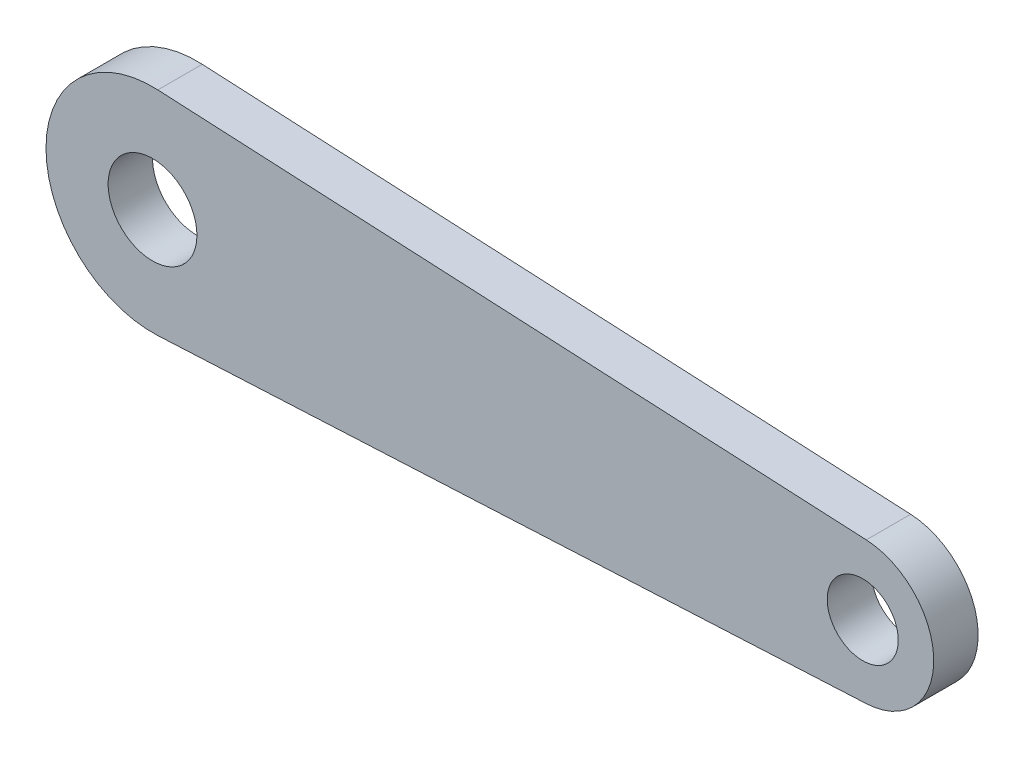
SolidWorks part; units mm, degrees
material "PE High Density"
ref_plane "Front Plane" through (0, 0, 0) normal (0, 0, 1) x (1, 0, 0)
ref_plane "Top Plane" through (0, 0, 0) normal (0, 1, 0) x (1, 0, 0)
ref_plane "Right Plane" through (0, 0, 0) normal (1, 0, 0) x (0, 0, -1)
sketch "Sketch1" plane through (0, 0, 0) normal (0, 0, 1) x (1, 0, 0)
  line L0 (0, -994.956) -> (0, 48752.8433) construction
  line L1 (0.381, 7.6105) -> (51.054, 5.0736)
  line L2 (51.054, -5.0736) -> (0.381, -7.6105)
  arc A0 (0.381, 7.6105) -> (0.381, -7.6105) centre (0, 0) ccw
  arc A2 (51.054, -5.0736) -> (51.054, 5.0736) centre (50.8, 0) ccw
  circle A4 centre (0, 0) radius 3.175
  circle A5 centre (50.8, 0) radius 2.54
  dimension "D1" = 10.16
  dimension "D3" = 7.62
  dimension "D4" = 6.35
  dimension "D5" = 5.08
  dimension "D2" = 50.8
extrude "Boss-Extrude1" add sketch "Sketch1" along normal blind 3.175
